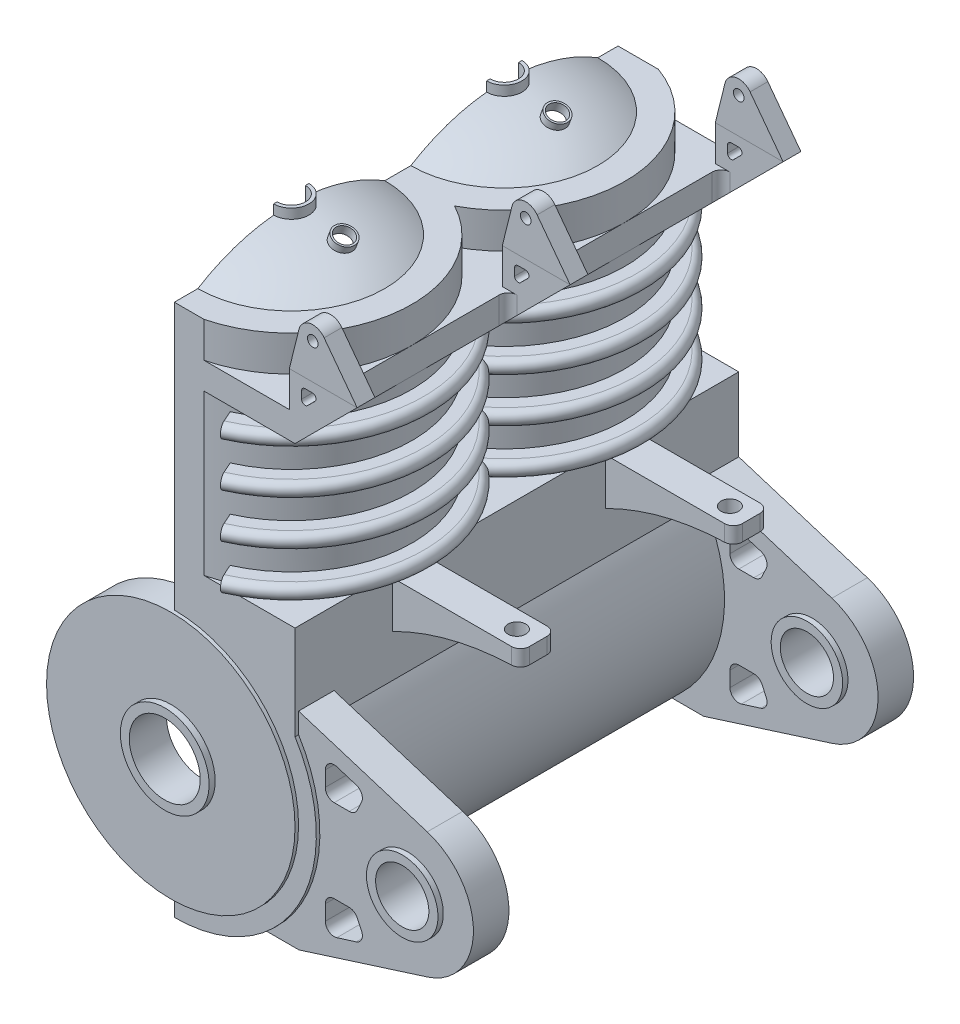
SolidWorks part; units mm, degrees
ref_plane "Front Plane" through (0, 0, 0) normal (0, 0, 1) x (1, 0, 0)
ref_plane "Top Plane" through (0, 0, 0) normal (0, 1, 0) x (1, 0, 0)
ref_plane "Right Plane" through (0, 0, 0) normal (1, 0, 0) x (0, 0, -1)
sketch "Sketch1" plane through (0, 0, 0) normal (0, 0, 1) x (1, 0, 0)
  line L0 (0, 0) -> (0, 28.02)
  line L1 (0, 28.02) -> (6.8, 28.02)
  line L3 (6.8, 12.2143) -> (6.8, 28.02)
  arc A1 (0, 0) -> (6.8, 12.2143) centre (0, 8) ccw
  dimension "D3" = 8
  dimension "D1" = 6.8
  dimension "D2" = 28.02
extrude "Boss-Extrude1" add sketch "Sketch1" along normal blind 25
sketch "Sketch2" plane through (0, 28.02, 0) normal (0, 1, 0) x (1, 0, 0)
  line L0 (0, -25) -> (0, 0) construction
  line L1 (6.8, -25) -> (0, -25) construction
  circle A0 centre (0, -6.41) radius 5
  circle A1 centre (0, -18.41) radius 5
  dimension "D1" = 10
  dimension "D2" = 12
  dimension "D3" = 6.59
extrude "Cut-Extrude1" cut sketch "Sketch2" against normal blind 20
sketch "Sketch3" plane through (0, 0, 25) normal (0, 0, 1) x (1, 0, 0)
  circle A0 centre (0, 8) radius 7
  dimension "D1" = 14
extrude "Cut-Extrude2" cut sketch "Sketch3" against normal through all
ref_plane "Plane1" through (0, 26.52, 0) normal (0, 1, 0) x (1, 0, 0)
sketch "Sketch4" plane through (0, 26.52, 0) normal (0, 1, 0) x (1, 0, 0)
  line L0 (0, 0.39) -> (8.7589, 0.39)
  line L1 (8.7589, 0.39) -> (8.7589, -25.21)
  line L2 (8.7589, -25.21) -> (0, -25.21)
  arc A6 (0, -25.21) -> (0, -11.61) centre (0, -18.41) ccw
  arc A7 (0, -25.21) -> (3.2, -12.41) centre (0, -18.41) ccw
  arc A9 (0, -13.21) -> (0, 0.39) centre (0, -6.41) ccw
  arc A10 (3.2, -12.41) -> (0, 0.39) centre (0, -6.41) ccw
  dimension "D1" = 1.8
  dimension "D2" = 1.8
extrude "Cut-Extrude3" cut sketch "Sketch4" against normal blind 9
sketch "Sketch5" plane through (0, 0, 0) normal (-1, 0, 0) x (0, 0, 1)
  line L0 (0, 28.02) -> (0, 15) construction
  line L1 (0.17, 27.17) -> (0.68, 27.17)
  line L2 (0.17, 27.17) -> (0.17, 17.17)
  line L3 (0.17, 17.17) -> (0.68, 17.17)
  line L4 (0.68, 27.17) -> (0.68, 17.17)
  line L5 (0.17, 27.17) -> (0.68, 17.17) construction
  line L6 (0.17, 17.17) -> (0.68, 27.17) construction
  line L7 (1.41, 28.02) -> (0, 28.02) construction
  line L8 (0, 15) -> (1.41, 15) construction
  line L9 (0.17, 25.87) -> (-1.07, 25.87)
  line L10 (0.17, 25.87) -> (0.17, 25.07)
  line L11 (0.17, 25.07) -> (-1.07, 25.07)
  line L13 (0.17, 23.37) -> (-1.07, 23.37)
  line L14 (0.17, 23.37) -> (0.17, 22.57)
  line L15 (0.17, 22.57) -> (-1.07, 22.57)
  line L17 (0.17, 20.87) -> (-1.07, 20.87)
  line L18 (0.17, 20.87) -> (0.17, 20.07)
  line L19 (0.17, 20.07) -> (-1.07, 20.07)
  line L21 (0.17, 18.37) -> (-1.07, 18.37)
  line L22 (0.17, 18.37) -> (0.17, 17.57)
  line L23 (0.17, 17.57) -> (-1.07, 17.57)
  line L25 (6.41, 28.02) -> (6.41, 32.2101) construction
  line L26 (11.41, 28.02) -> (1.41, 28.02) construction
  arc A0 (-1.07, 18.37) -> (-1.07, 17.57) centre (-1.07, 17.97) ccw
  arc A1 (-1.07, 20.87) -> (-1.07, 20.07) centre (-1.07, 20.47) ccw
  arc A2 (-1.07, 23.37) -> (-1.07, 22.57) centre (-1.07, 22.97) ccw
  arc A3 (-1.07, 25.87) -> (-1.07, 25.07) centre (-1.07, 25.47) ccw
  point P0 (0.425, 22.17)
  dimension "D1" = 10
  dimension "D2" = 0.51
  dimension "D3" = 0.68
  dimension "D4" = 0.85
  dimension "D5" = 1.07
  dimension "D6" = 0.8
  dimension "D7" = 2.15
  dimension "D8" = 2.97
  dimension "D9" = 5.47
  dimension "D10" = 7.97
revolve "Revolve1" add sketch "Sketch5" angle 156 about L25 region at (0, 22.17, 0.425) region at (0, 25.47, 0.085) region at (0, 25.47, -0.695) region at (0, 22.97, 0.085) region at (0, 17.97, 0.085) region at (0, 22.97, -0.695) region at (0, 17.97, -0.695) region at (0, 20.47, 0.085) region at (0, 20.47, -0.695) reverse direction yes
pattern_linear "LPattern1" count 2 spacing 12 along (0, 0, 1) of "Revolve1"
sketch "Sketch6" plane through (0, 28.02, 0) normal (0, 1, 0) x (1, 0, 0)
  circle A1 centre (0, -6.41) radius 5
extrude "Cut-Extrude5" cut sketch "Sketch6" against normal blind 12
sketch "Sketch7" plane through (0, 0, 0) normal (0, 0, -1) x (-1, 0, 0)
  circle A0 centre (0, 8) radius 7
  circle A1 centre (0, 8) radius 2.5
  arc M8 (0, 1) -> (0, 15) centre (0, 8) cw
  dimension "D1" = 5
extrude "Boss-Extrude2" add sketch "Sketch7" along normal blind 0.5 and the other way blind 1 contours A0 A1 M8 region at (-4.8097, 3.1903, 0)
pattern_linear "LPattern2" count 3 spacing 12 along (0, 0, 1) of "Boss-Extrude2"
sketch "Sketch8" plane through (0, 0, 25) normal (0, 0, 1) x (1, 0, 0)
  circle A0 centre (0, 8) radius 2.5 construction
  circle A1 centre (0, 8) radius 2.5
  arc A4 (0, 1) -> (0, 15) centre (0, 8) ccw
  arc A5 (0, 15) -> (0, 1) centre (0, 8) ccw
  arc A6 (0, 1) -> (0, 15) centre (0, 8) ccw
  arc A7 (0, 15) -> (0, 1) centre (0, 8) ccw
  dimension "D1" = 0
extrude "Boss-Extrude3" add sketch "Sketch8" along normal blind 0.2
sketch "Sketch9" plane through (0, 0, -0.5) normal (0, 0, -1) x (-1, 0, 0)
  circle A0 centre (0, 8) radius 2.5 construction
  circle A1 centre (0, 8) radius 2.5
  circle A2 centre (0, 8) radius 2
  dimension "D1" = 4
extrude "Boss-Extrude4" add sketch "Sketch9" along normal blind 0.5 and the other way blind 1.6
pattern_linear "LPattern4" count 3 spacing 12.22 along (0, 0, 1) of "Boss-Extrude4"
sketch "Sketch10" plane through (0, 28.02, 0) normal (0, 1, 0) x (1, 0, 0)
  line L0 (0, -25) -> (0, -23.41) construction
  line L1 (0, -13.41) -> (0, -11.41) construction
  line L2 (0, -1.41) -> (0, 0) construction
  line L3 (0, -25) -> (0, -23.41)
  line L4 (0, -13.41) -> (0, -11.41)
  line L5 (0, -1.41) -> (0, 0)
  line L6 (1.6769, -25) -> (0, -25)
  line L7 (0, 0) -> (2.2698, 0)
  arc A0 (1.6769, -25) -> (6.8, -18.41) centre (0, -18.41) ccw construction
  arc A1 (6.8, -18.41) -> (3.2, -12.41) centre (0, -18.41) ccw construction
  arc A2 (3.2, -12.41) -> (6.8, -6.41) centre (0, -6.41) ccw construction
  arc A3 (0, -23.41) -> (0, -13.41) centre (0, -18.41) ccw construction
  arc A4 (6.8, -6.41) -> (2.2698, 0) centre (0, -6.41) ccw construction
  arc A5 (0, -11.41) -> (0, -1.41) centre (0, -6.41) ccw construction
  arc A6 (1.6769, -25) -> (6.8, -18.41) centre (0, -18.41) ccw
  arc A7 (6.8, -18.41) -> (3.2, -12.41) centre (0, -18.41) ccw
  arc A8 (3.2, -12.41) -> (6.8, -6.41) centre (0, -6.41) ccw
  arc A9 (0, -23.41) -> (0, -13.41) centre (0, -18.41) ccw
  arc A10 (6.8, -6.41) -> (2.2698, 0) centre (0, -6.41) ccw
  arc A11 (0, -11.41) -> (0, -1.41) centre (0, -6.41) ccw
extrude "Boss-Extrude5" add sketch "Sketch10" along normal blind 2 contours L7 A10 A8 A7 A6 L6 L3 A9 L4 A11 L5
sketch "Sketch11" plane through (0, 0, 0) normal (0, 0, -1) x (-1, 0, 0)
  line L0 (0, 8) -> (-15.3136, 8) construction
  line L1 (-8.9771, 7.56) -> (-12.94, 7.56) construction
  line L2 (-6.8, 13.3702) -> (-14.0486, 11.1005)
  line L3 (-6.8, 12.2143) -> (-6.8, 17.52) construction
  line L4 (-14.0626, 4.0239) -> (-6.823, 1.7256)
  line L5 (-6.823, 1.7256) -> (-4.963, 1.7256)
  line L6 (-6.8, 12.2143) -> (-6.8, 13.3702)
  arc A1 (-14.0486, 11.1005) -> (-14.0626, 4.0239) centre (-12.94, 7.56) ccw
  arc A2 (-6.8, 12.2143) -> (0, 0) centre (0, 8) ccw construction
  arc A3 (-6.8, 12.2143) -> (-4.963, 1.7256) centre (0, 8) ccw
  circle A4 centre (-12.94, 7.56) radius 2.015
  dimension "D3" = 4.03
  dimension "D4" = 3.71
  dimension "D1" = 0.44
  dimension "D2" = 12.94
  dimension "D5" = 35
  dimension "D6" = 1.86
extrude "Boss-Extrude6" add sketch "Sketch11" against normal blind 2
pattern_linear "LPattern5" count 2 spacing 22.8 along (0, 0, 1) of "Boss-Extrude6"
sketch "Sketch12" plane through (0, 0, 0) normal (0, 0, -1) x (-1, 0, 0)
  circle A0 centre (-12.94, 7.56) radius 2.015 construction
  circle A1 centre (-12.94, 7.56) radius 2.015
  circle A2 centre (-12.94, 7.56) radius 1.5
  dimension "D1" = 3
extrude "Boss-Extrude7" add sketch "Sketch12" along normal blind 0.3 and the other way blind 2.3
pattern_linear "LPattern6" count 2 spacing 22.8 along (0, 0, 1) of "Boss-Extrude7"
sketch "Sketch13" plane through (0, 0, 0) normal (0, 0, -1) x (-1, 0, 0)
  line L0 (-8.3051, 10.4022) -> (-8.3051, 11.2536)
  line L1 (-8.9545, 11.7307) -> (-10.0443, 11.3895)
  line L2 (-10.3471, 10.699) -> (-10.1065, 10.1888)
  line L3 (-9.6543, 9.9022) -> (-8.8051, 9.9022)
  line L4 (-12.94, 7.56) -> (-8.7724, 7.56) construction
  line L5 (-10.3471, 4.421) -> (-10.1065, 4.9312)
  line L6 (-8.9545, 3.3893) -> (-10.0443, 3.7305)
  line L7 (-8.3051, 4.7178) -> (-8.3051, 3.8664)
  line L8 (-9.6543, 5.2178) -> (-8.8051, 5.2178)
  arc A0 (-10.3471, 4.421) -> (-10.0443, 3.7305) centre (-9.8949, 4.2077) ccw
  arc A1 (-8.9545, 3.3893) -> (-8.3051, 3.8664) centre (-8.8051, 3.8664) ccw
  arc A2 (-8.3051, 4.7178) -> (-8.8051, 5.2178) centre (-8.8051, 4.7178) ccw
  arc A3 (-10.1065, 4.9312) -> (-9.6543, 5.2178) centre (-9.6543, 4.7178) cw
  arc A4 (-10.1065, 10.1888) -> (-9.6543, 9.9022) centre (-9.6543, 10.4022) ccw
  arc A5 (-8.3051, 10.4022) -> (-8.8051, 9.9022) centre (-8.8051, 10.4022) cw
  arc A6 (-8.3051, 11.2536) -> (-8.9545, 11.7307) centre (-8.8051, 11.2536) ccw
  arc A7 (-10.0443, 11.3895) -> (-10.3471, 10.699) centre (-9.8949, 10.9123) ccw
  point P13 (-10.592, 3.902)
  point P16 (-8.3051, 3.1859)
  point P19 (-8.3051, 5.2178)
  point P22 (-9.9712, 5.2178)
  point P25 (-9.9712, 9.9022)
  point P28 (-8.3051, 9.9022)
  point P31 (-8.3051, 11.9341)
  point P34 (-10.592, 11.218)
  dimension "D1" = 0.5
extrude "Cut-Extrude6" cut sketch "Sketch13" against normal up to surface (24.8 mm away) up to face at (10.925, 7.56, 24.8)
sketch "Sketch14" plane through (0, 0, 0) normal (-1, 0, 0) x (0, 0, 1)
  line L0 (18.41, 30.02) -> (18.41, 21.52) construction
  line L1 (23.41, 30.02) -> (13.41, 30.02) construction
  line L2 (13.41, 30.02) -> (11.41, 30.02) construction
  line L3 (13.1422, 30.02) -> (13.3737, 30.02)
  line L4 (18.41, 31.52) -> (18.41, 31.4)
  arc A0 (13.1422, 30.02) -> (18.41, 31.52) centre (18.41, 21.52) cw
  arc A1 (13.3737, 30.02) -> (18.41, 31.4) centre (18.41, 21.52) cw
  arc A2 (13.2054, 29.918) -> (18.41, 31.4) centre (18.41, 21.52) cw construction
  dimension "D1" = 10
  dimension "D2" = 8.5
  dimension "D3" = 0.12
revolve "Revolve2" add sketch "Sketch14" angle 180 about L0
pattern_linear "LPattern7" count 2 spacing 12 along (0, 0, -1) of "Revolve2"
sketch "Sketch15" plane through (0, 30.02, 0) normal (0, 1, 0) x (1, 0, 0)
  line L0 (0, -13.1422) -> (0, -23.6778) construction
  line L1 (0, -1.1422) -> (0, -11.6778) construction
  circle A0 centre (0, -18.41) radius 0.995
  circle A1 centre (0, -6.41) radius 0.995
  dimension "D1" = 1.99
  dimension "D2" = 1.99
extrude "Cut-Extrude7" cut sketch "Sketch15" along normal blind 10.3
sketch "Sketch16" plane through (0, 30.02, 0) normal (0, 1, 0) x (1, 0, 0)
  line L0 (0, -5.415) -> (0, -5.61)
  line L1 (0, -7.405) -> (0, -7.21)
  line L2 (0, -17.61) -> (0, -17.415)
  line L3 (0, -19.405) -> (0, -19.21)
  arc A0 (0, -7.405) -> (0, -5.415) centre (0, -6.41) ccw construction
  arc A1 (0, -7.405) -> (0, -5.415) centre (0, -6.41) ccw
  arc A3 (0, -19.405) -> (0, -17.415) centre (0, -18.41) ccw construction
  arc A4 (0, -19.405) -> (0, -17.415) centre (0, -18.41) ccw
  arc A5 (0, -7.21) -> (0, -5.61) centre (0, -6.41) ccw
  arc A6 (0, -19.21) -> (0, -17.61) centre (0, -18.41) ccw
  dimension "D1" = 1.6
  dimension "D2" = 1.6
extrude "Boss-Extrude8" add sketch "Sketch16" along normal blind 0.8 from offset 1.2
ref_plane "Plane2" through (9.6482, 26.5083, 0) normal (0.342, 0.9397, 0) x (0, 0, -1)
sketch "Sketch17" plane through (9.6482, 26.5083, 0) normal (0.342, 0.9397, 0) x (0, 0, -1)
  line L0 (-6.41, 10.9515) -> (-6.41, 7.9515) construction
  line L1 (-7.21, 10.9515) -> (-7.405, 10.9515) construction
  circle A3 centre (-6.41, 7.9515) radius 0.6
  dimension "D1" = 1.2
  dimension "D2" = 3
sketch "Sketch18" plane through (0, 0, 0) normal (0, 0, -1) x (-1, 0, 0)
  line L0 (-6.8, 26.52) -> (-6.48, 26.52)
  line L1 (-6.8, 26.52) -> (-2.2698, 26.52) construction
  line L2 (-6.48, 26.52) -> (-6.48, 30.02)
  line L3 (-2.2698, 30.02) -> (-6.8, 30.02) construction
  line L4 (-6.48, 30.02) -> (-8.8, 30.02)
  line L5 (-8.8, 30.02) -> (-9.9243, 31.1443)
  line L6 (-10.0872, 30.9814) -> (-10.5114, 30.5572)
  line L7 (-10.6743, 30.3943) -> (-6.8, 26.52)
  line L8 (-7.7817, 29.4846) -> (-7.3694, 29.4846)
  line L9 (-7.1694, 29.2846) -> (-7.1694, 28.8723)
  line L10 (-7.5108, 28.7308) -> (-7.9231, 29.1431)
  arc A0 (-9.9243, 31.1443) -> (-10.6743, 30.3943) centre (-10.2993, 30.7693) ccw
  circle A1 centre (-10.2993, 30.7693) radius 0.3
  arc A2 (-7.1694, 28.8723) -> (-7.5108, 28.7308) centre (-7.3694, 28.8723) cw
  arc A3 (-7.3694, 29.4846) -> (-7.1694, 29.2846) centre (-7.3694, 29.2846) cw
  arc A4 (-7.7817, 29.4846) -> (-7.9231, 29.1431) centre (-7.7817, 29.2846) ccw
  point P24 (-7.3694, 29.4846)
  line M20 (-2.2698, 28.02) -> (-6.8, 28.02)
  line M21 (-6.8, 28.02) -> (-6.8, 26.52)
  line M22 (-6.8, 26.52) -> (-2.2698, 26.52)
  dimension "D5" = 0.6
  dimension "D6" = 0.2
  dimension "D1" = 135
  dimension "D2" = 0.32
  dimension "D3" = 2.32
  dimension "D4" = 1.59
extrude "Boss-Extrude9" add sketch "Sketch18" against normal blind 1 contours L5 A0 L7 L2 L4 A4 L8 A3 L9 A2 L10 A1 M21 M20 | L2 M22 M20 M21 region at (6.64, 27.27, 0) region at (8.2194, 29.1325, 0)
pattern_linear "LPattern8" count 3 spacing 12 along (0, 0, 1) of "Boss-Extrude9"
fillet "Fillet1" radius 0.5 4 edges at (6.8, 27.27, 1) (6.8, 27.27, 13) (6.8, 27.27, 12) (6.8, 27.27, 24)
sketch "Sketch19" plane through (0, 0, 0) normal (0, 0, -1) x (-1, 0, 0)
  line L0 (-6.8, 17.2183) -> (-14, 17.2183)
  line L1 (-6.8, 13.3702) -> (-6.8, 17.52) construction
  line L2 (-14, 17.2183) -> (-14, 16.3183)
  line L3 (-6.8, 14.6067) -> (-6.8, 17.2183)
  arc A0 (-14, 16.3183) -> (-6.8, 14.6067) centre (-14, 0.3183) cw
  point P7 (-14, 15.7678)
  point P8 (-6.8, 13.8994)
  dimension "D1" = 7.2
  dimension "D2" = 0.9
  dimension "D3" = 16
extrude "Boss-Extrude12" add sketch "Sketch19" against normal blind 2 from offset 5.5 offset against normal yes
pattern_linear "LPattern9" count 2 spacing 12 along (0, 0, 1) of "Boss-Extrude12"
sketch "Sketch20" plane through (0, 17.2183, 0) normal (0, 1, 0) x (1, 0, 0)
  line L0 (14, -7.5) -> (14, -5.5) construction
  line L1 (14, -19.5) -> (14, -17.5) construction
  line L2 (12.8, -6.5) -> (14, -6.5) construction
  line L3 (12.8, -18.5) -> (14, -18.5) construction
  circle A0 centre (12.8, -18.5) radius 0.5
  circle A1 centre (12.8, -6.5) radius 0.5
  point P6 (14, -6.5)
  point P9 (14, -18.5)
  dimension "D1" = 1
  dimension "D2" = 1.2
  dimension "D3" = 1.2
extrude "Cut-Extrude10" cut sketch "Sketch20" against normal up to surface (0.9451 mm away) up to face at (10.3498, 15.6735, 18.5)
fillet "Fillet2" radius 0.5 4 edges at (14, 16.7683, 17.5) (14, 16.7683, 7.5) (14, 16.7683, 5.5) (14, 16.7683, 19.5)
sketch "Sketch21" plane through (0, 0, 0) normal (0, 0, -1) x (-1, 0, 0)
  line L0 (-6.48, 30.02) -> (-8.8, 30.02) construction
  line L1 (-8.298, 32.1143) -> (-11.1441, 32.1143)
  line L2 (-8.298, 32.1143) -> (-8.298, 30.02)
  line L3 (-8.298, 30.02) -> (-11.1441, 30.02)
  line L4 (-11.1441, 32.1143) -> (-11.1441, 30.02)
extrude "Cut-Extrude11" cut sketch "Sketch21" against normal through all
sketch "Sketch22" plane through (0, 0, 0) normal (0, 0, -1) x (-1, 0, 0)
  line L0 (-6.48, 30.02) -> (-7.0235, 32.2125)
  line L1 (-8.44, 32.5) -> (-10.3, 30.02)
  line L2 (-10.3, 30.02) -> (-6.48, 30.02)
  line L3 (0, 32.02) -> (0, 31.4704) construction
  circle A0 centre (-7.8, 32.02) radius 0.3
  arc A1 (-7.0235, 32.2125) -> (-8.44, 32.5) centre (-7.8, 32.02) ccw
  dimension "D2" = 0.6
  dimension "D3" = 0.8
  dimension "D1" = 7.8
  dimension "D4" = 2
extrude "Boss-Extrude13" add sketch "Sketch22" against normal blind 1 separate body
pattern_linear "LPattern10" count 3 spacing 12 along (0, 0, 1) of "Boss-Extrude13"
extrude "Cut-Extrude19" cut sketch "Sketch17" along normal up to surface (1.9414 mm away) up to face at (1.5657, 30.8673, 6.41)
sketch "Sketch25" plane through (9.6482, 26.5083, 0) normal (0.342, 0.9397, 0) x (0, 0, -1)
  line L0 (-18.41, 10.9515) -> (-18.41, 7.9515) construction
  line L2 (-19.21, 10.9515) -> (-19.405, 10.9515) construction
  circle A1 centre (-18.41, 7.9515) radius 0.6
  dimension "D1" = 3
  dimension "D2" = 1.2
extrude "Cut-Extrude20" cut sketch "Sketch25" along normal up to surface (1.9414 mm away) up to face at (1.5657, 30.8673, 18.41)
extrude "Extrude-Thin3" add sketch "Sketch17<9>" along normal blind 0.5 from offset 1.9 thin thin type one direction reverse wall 0.1
sketch "Sketch17<9>" plane through (9.6482, 26.5083, 0) normal (0.342, 0.9397, 0) x (0, 0, -1) same geometry as "Sketch17"
extrude "Extrude-Thin4" add sketch "Sketch25<2>" along normal blind 0.5 from offset 1.9 thin thin type one direction reverse wall 0.1
sketch "Sketch25<2>" plane through (9.6482, 26.5083, 0) normal (0.342, 0.9397, 0) x (0, 0, -1) same geometry as "Sketch25"
